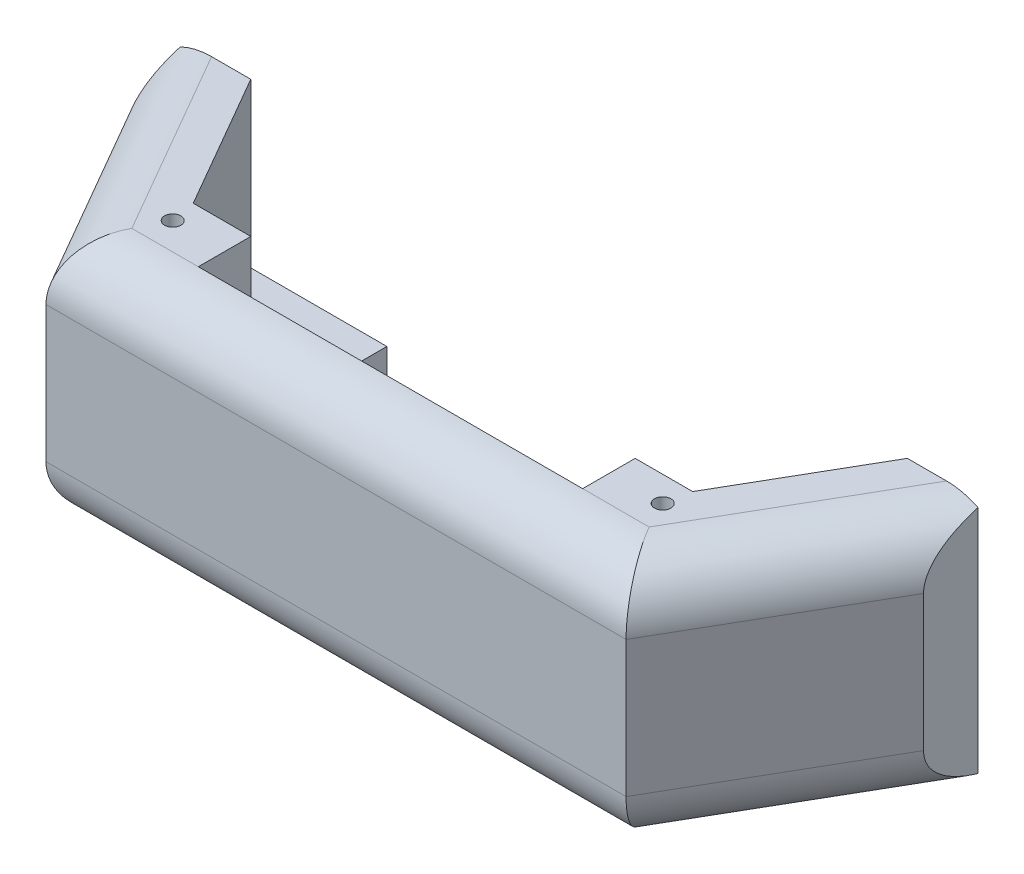
SolidWorks part; units mm, degrees
material "ABS"
ref_plane "Alzado" through (0, 0, 0) normal (0, 0, 1) x (1, 0, 0)
ref_plane "Planta" through (0, 0, 0) normal (0, 1, 0) x (1, 0, 0)
ref_plane "Vista lateral" through (0, 0, 0) normal (1, 0, 0) x (0, 0, -1)
sketch "Sketch2" plane through (0, 0, 0) normal (0, 1, 0) x (1, 0, 0)
  line L0 (-73.275, 22.3205) -> (73.275, 22.3205)
  line L1 (73.275, 22.3205) -> (73.275, 12.3205)
  line L2 (73.275, 12.3205) -> (53.275, -22.3205)
  line L3 (53.275, -22.3205) -> (-53.275, -22.3205)
  line L4 (-53.275, -22.3205) -> (-73.275, 12.3205)
  line L5 (-73.275, 12.3205) -> (-73.275, 22.3205)
  line L6 (0, 22.3205) -> (0, -22.3205) construction
  dimension "D1" = 10
  dimension "D2" = 40
  dimension "D3" = 120
  dimension "D4" = 106.55
extrude "Boss-Extrude2" add sketch "Sketch2" along normal blind 45
fillet "Fillet2" radius 10 3 edges at (63.275, 45, 5) (0, 45, 22.3205) (-63.275, 45, 5)
fillet "Fillet3" radius 10 3 edges at (-63.275, 0, 5) (63.275, 0, 5) (0, 0, 22.3205)
sketch "Sketch3" plane through (0, 45, 0) normal (0, 1, 0) x (1, 0, 0)
  line L0 (67.5015, 22.3205) -> (-67.5015, 22.3205) construction
  line L1 (-35.3, 22.3205) -> (35.3, 22.3205)
  line L2 (-35.3, 22.3205) -> (-35.3, -12.3205)
  line L3 (-35.3, -12.3205) -> (35.3, -12.3205)
  line L4 (35.3, 22.3205) -> (35.3, -12.3205)
  line L5 (0, -12.3205) -> (0, 22.3205) construction
  line L6 (-47.5015, -12.3205) -> (47.5015, -12.3205) construction
  point P11 (0, 22.3205)
  dimension "D1" = 70.6
extrude "Cut-Extrude1" cut sketch "Sketch3" against normal offset from surface (44 mm away) 1 up to face at (0, 0, -5)
sketch "Sketch4" plane through (0, 45, 0) normal (0, 1, 0) x (1, 0, 0)
  line L0 (0, 22.3205) -> (0, -22.3205) construction
  line L1 (35.3, 22.3205) -> (-35.3, 22.3205) construction
  line L2 (53.275, -22.3205) -> (-53.275, -22.3205) construction
  circle A0 centre (-45, -7.3205) radius 1.5
  circle A1 centre (45, -7.3205) radius 1.5
  dimension "D1" = 15
  dimension "D3" = 3
  dimension "D2" = 45
extrude "Cut-Extrude2" cut sketch "Sketch4" against normal blind 10
sketch "Sketch5" plane through (0, 45, 0) normal (0, 1, 0) x (1, 0, 0)
  line L0 (-60.3, 22.3205) -> (-35.3, 22.3205)
  line L1 (-35.3, 22.3205) -> (-67.5015, 22.3205) construction
  line L2 (-35.3, 22.3205) -> (-35.3, -2.6795)
  line L3 (-35.3, 22.3205) -> (-35.3, -12.3205) construction
  line L4 (-35.3, -2.6795) -> (-45.8662, -2.6795)
  line L5 (-45.8662, -2.6795) -> (-60.3, 22.3205)
  line L6 (-67.5015, 22.3205) -> (-47.5015, -12.3205) construction
  line L7 (0, 22.3205) -> (0, -12.3205) construction
  line L8 (35.3, 22.3205) -> (-35.3, 22.3205) construction
  line L9 (-35.3, -12.3205) -> (35.3, -12.3205) construction
  line L10 (35.3, -2.6795) -> (45.8662, -2.6795)
  line L11 (35.3, 22.3205) -> (35.3, -2.6795)
  line L12 (60.3, 22.3205) -> (35.3, 22.3205)
  line L13 (45.8662, -2.6795) -> (60.3, 22.3205)
  dimension "D1" = 25
  dimension "D2" = 25
extrude "Cut-Extrude3" cut sketch "Sketch5" against normal offset from surface (30 mm away) 15 up to face at (0, 0, -5)
sketch "Sketch6" plane through (0, 0, 0) normal (0, -1, 0) x (-1, 0, 0)
  line L0 (0, -12.3205) -> (0, 22.3205) construction
  line L1 (-47.5015, -12.3205) -> (47.5015, -12.3205) construction
  line L2 (-67.5015, 22.3205) -> (67.5015, 22.3205) construction
  circle A0 centre (40, -2.3205) radius 1.5
  circle A1 centre (-40, -2.3205) radius 1.5
  circle A2 centre (60, 17.6795) radius 1.5
  circle A3 centre (-60, 17.6795) radius 1.5
  dimension "D1" = 40
  dimension "D3" = 3
  dimension "D4" = 60
  dimension "D2" = 10
  dimension "D5" = 30
extrude "Cut-Extrude4" cut sketch "Sketch6" against normal blind 10
sketch "Sketch7" plane through (0, 0, 0) normal (0, -1, 0) x (-1, 0, 0)
  line L0 (0, -12.3205) -> (0, 22.3205) construction
  line L1 (-47.5015, -12.3205) -> (47.5015, -12.3205) construction
  line L2 (-67.5015, 22.3205) -> (67.5015, 22.3205) construction
  circle A0 centre (40, 7.6795) radius 1.5
  circle A1 centre (-40, 7.6795) radius 1.5
  dimension "D1" = 3
  dimension "D2" = 40
  dimension "D3" = 20
extrude "Cut-Extrude5" cut sketch "Sketch7" against normal blind 10
